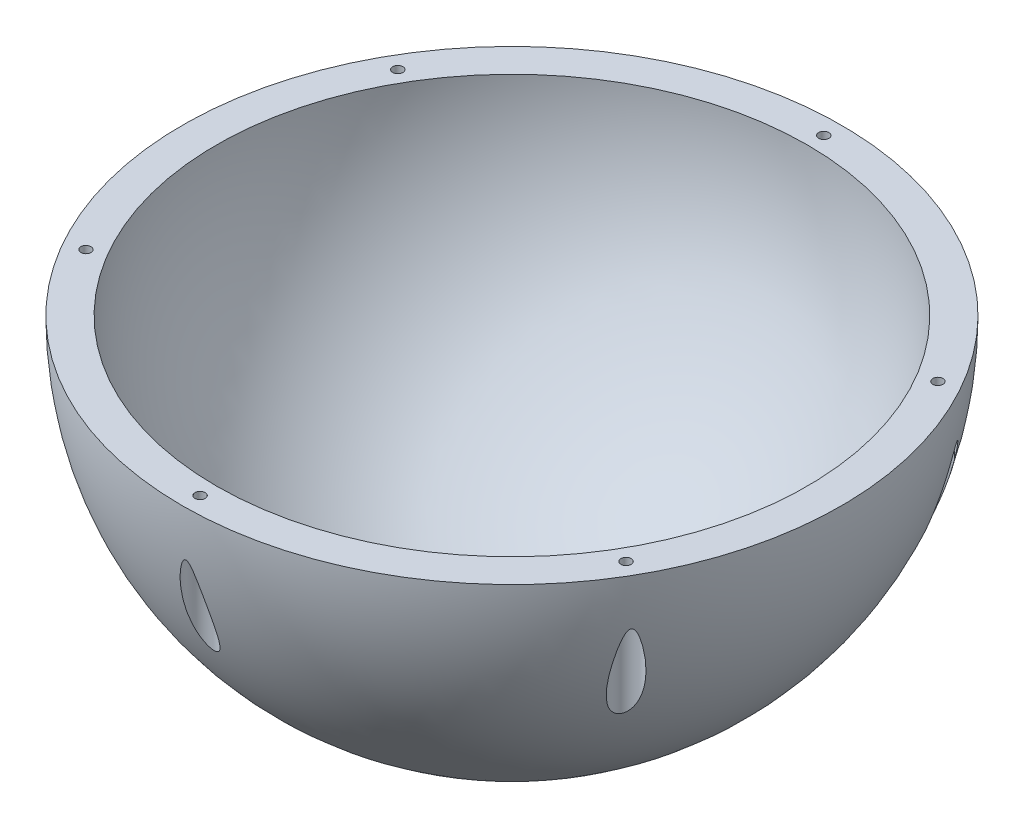
SolidWorks part; units mm, degrees
ref_plane "Front Plane" through (0, 0, 0) normal (0, 0, 1) x (1, 0, 0)
ref_plane "Top Plane" through (0, 0, 0) normal (0, 1, 0) x (1, 0, 0)
ref_plane "Right Plane" through (0, 0, 0) normal (1, 0, 0) x (0, 0, -1)
sketch "Sketch1" plane through (0, 0, 0) normal (0, 1, 0) x (1, 0, 0)
  circle A0 centre (0, 0) radius 92.075
extrude "Boss-Extrude3" add sketch "Sketch1" along normal blind 92.075 contours A0
sketch "Sketch3" plane through (0, 92.075, 0) normal (0, 1, 0) x (1, 0, 0)
  circle A0 centre (0, 0) radius 82.55
extrude "Cut-Extrude1" cut sketch "Sketch3" against normal blind 82.55 contours A0
fillet "Fillet12" radius 82.55 1 edges at (0, 9.525, 82.55)
fillet "Fillet13" radius 92.075 1 edges at (0, 0, 92.075)
sketch "Sketch6" plane through (0, 92.075, 0) normal (0, 1, 0) x (1, 0, 0)
  circle A0 centre (0, 87.122) radius 3.937
  circle A1 centre (75.4499, 43.561) radius 3.937
  circle A2 centre (75.4499, -43.561) radius 3.937
  circle A3 centre (0, -87.122) radius 3.937
  circle A4 centre (-75.4499, -43.561) radius 3.937
  circle A5 centre (-75.4499, 43.561) radius 3.937
  circle A6 centre (0, 0) radius 82.55 construction
  dimension "D1" = 87.122
  dimension "D2" = 87.122
  dimension "D3" = 87.122
  dimension "D4" = 87.122
  dimension "D5" = 87.122
  dimension "D6" = 87.122
extrude "Cut-Extrude3" cut sketch "Sketch6" against normal blind 50.8
sketch "Sketch8" plane through (0, 92.075, 0) normal (0, 1, 0) x (1, 0, 0)
  circle A0 centre (-75.4499, -43.561) radius 3.937
  circle A1 centre (0, -87.122) radius 1.4224
  circle A3 centre (0, -87.122) radius 3.937
  circle A4 centre (75.4499, -43.561) radius 3.937
  circle A5 centre (75.4499, 43.561) radius 3.937
  circle A6 centre (0, 87.122) radius 3.937
  circle A7 centre (-75.4499, 43.561) radius 3.937
  circle A8 centre (-75.4499, -43.561) radius 1.4224
  circle A9 centre (75.4499, -43.561) radius 1.4224
  circle A10 centre (75.4499, 43.561) radius 1.4224
  circle A11 centre (0, 87.122) radius 1.4224
  circle A12 centre (-75.4499, 43.561) radius 1.4224
extrude "Boss-Extrude6" add sketch "Sketch8" against normal blind 3.175
